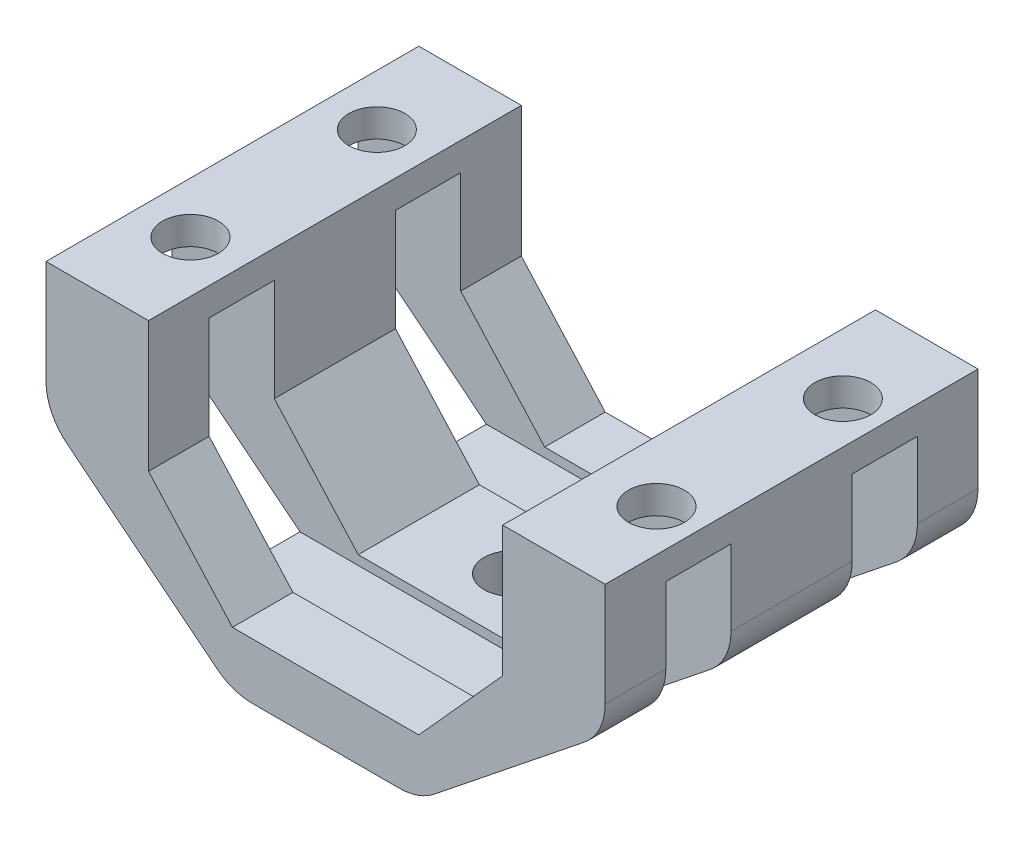
SolidWorks part; units mm, degrees
ref_plane "Alzado" through (0, 0, 0) normal (0, 0, 1) x (1, 0, 0)
ref_plane "Planta" through (0, 0, 0) normal (0, 1, 0) x (1, 0, 0)
ref_plane "Vista lateral" through (0, 0, 0) normal (1, 0, 0) x (0, 0, -1)
sketch "Croquis1" plane through (0, 0, 0) normal (0, 0, 1) x (1, 0, 0)
  line L0 (0, 0) -> (0, -5) construction
  line L21 (0, 0) -> (-4.5, 0) construction
  line L22 (-10, 0) -> (0, -8)
  line L23 (-4.5, 0) -> (-10, 0)
  line L24 (-4.5, 0) -> (-4.5, 7)
  line L25 (-4.5, 7) -> (-10, 7)
  line L26 (-10, 0) -> (-10, 7)
  line L27 (0, -5) -> (10, -5)
  line L28 (0, -5) -> (0, -8)
  line L29 (0, -8) -> (10, -8)
  line L30 (5, -5) -> (5, -8)
  line L31 (0, -5) -> (-4.5, 0)
  line L32 (10, -5) -> (10, -8)
  line L33 (20, 0) -> (10, -8)
  line L34 (10, -5) -> (14.5, 0)
  line L35 (14.5, 7) -> (20, 7)
  line L36 (20, 0) -> (20, 7)
  line L37 (14.5, 0) -> (20, 0)
  line L38 (14.5, 0) -> (14.5, 7)
  dimension "D1" = 7
  dimension "D2" = 4.5
  dimension "D3" = 5
  dimension "D4" = 3
  dimension "D5" = 5
  dimension "D6" = 5.5
extrude "Saliente-Extruir1" add sketch "Croquis1" along normal blind 20 contours L26 L23 L24 L25 | L28 L31 L23 L22 | L30 L27 L28 L29 | L32 L27 L30 L29 | L37 L34 L32 L33 | L38 L37 L36 L35 region at (-4.0507, -3.058, 0) region at (-7.25, 3.5, 0) region at (2.5, -6.5, 0) region at (7.5, -6.5, 0) region at (14.0507, -3.058, 0) region at (17.25, 3.5, 0)
sketch "Croquis2" plane through (-10, 0, 0) normal (-1, 0, 0) x (0, 0, 1)
  line L0 (10, 7) -> (10, 0) construction
  line L2 (20, 7) -> (0, 7) construction
  line L3 (20, 0) -> (0, 0) construction
  line L8 (0, 7) -> (10, 7) construction
  line L9 (5, 7) -> (5, 0) construction
  line L15 (16.75, 5.5) -> (13.25, 5.5)
  line L16 (3.25, -5.5) -> (6.75, -5.5)
  line L17 (3.25, -5.5) -> (3.25, 5.5)
  line L18 (3.25, 5.5) -> (6.75, 5.5)
  line L19 (6.75, -5.5) -> (6.75, 5.5)
  line L20 (3.25, -5.5) -> (6.75, 5.5) construction
  line L21 (3.25, 5.5) -> (6.75, -5.5) construction
  line L22 (13.25, -5.5) -> (13.25, 5.5)
  line L23 (16.75, -5.5) -> (13.25, -5.5)
  line L24 (16.75, -5.5) -> (16.75, 5.5)
  point P14 (5, -0.8486)
  point P15 (5, -0.3413)
  point P16 (5, 0)
  dimension "D1" = 3.5
  dimension "D2" = 1.5
extrude "Cortar-Extruir3" cut sketch "Croquis2" against normal through all
sketch "Croquis3" plane through (0, 7, 0) normal (0, 1, 0) x (1, 0, 0)
  line L0 (-7.25, 0) -> (-7.25, -5) construction
  line L1 (-4.5, 0) -> (-10, 0) construction
  circle A0 centre (-7.25, -5) radius 1.5
  circle A1 centre (17.75, -5) radius 1.5
  circle A2 centre (17.75, -15) radius 1.5
  circle A3 centre (-7.25, -15) radius 1.5
  dimension "D1" = 3
  dimension "D2" = 2
  dimension "D3" = 2
extrude "Cortar-Extruir4" cut sketch "Croquis3" against normal through all
fillet "Redondeo1" radius 3 8 edges at (10, -8, 10) (20, 0, 1.625) (20, 0, 18.375) (20, 0, 10) (0, -8, 10) (-10, 0, 18.375) (-10, 0, 1.625) (-10, 0, 10)
sketch "Croquis4" plane through (0, -5, 0) normal (0, 1, 0) x (1, 0, 0)
  line L0 (5, 0) -> (5, -20) construction
  line L1 (0, 0) -> (10, 0) construction
  line L2 (0, -20) -> (10, -20) construction
  circle A0 centre (5, -10) radius 1.5
extrude "Cortar-Extruir5" cut sketch "Croquis4" against normal through all
